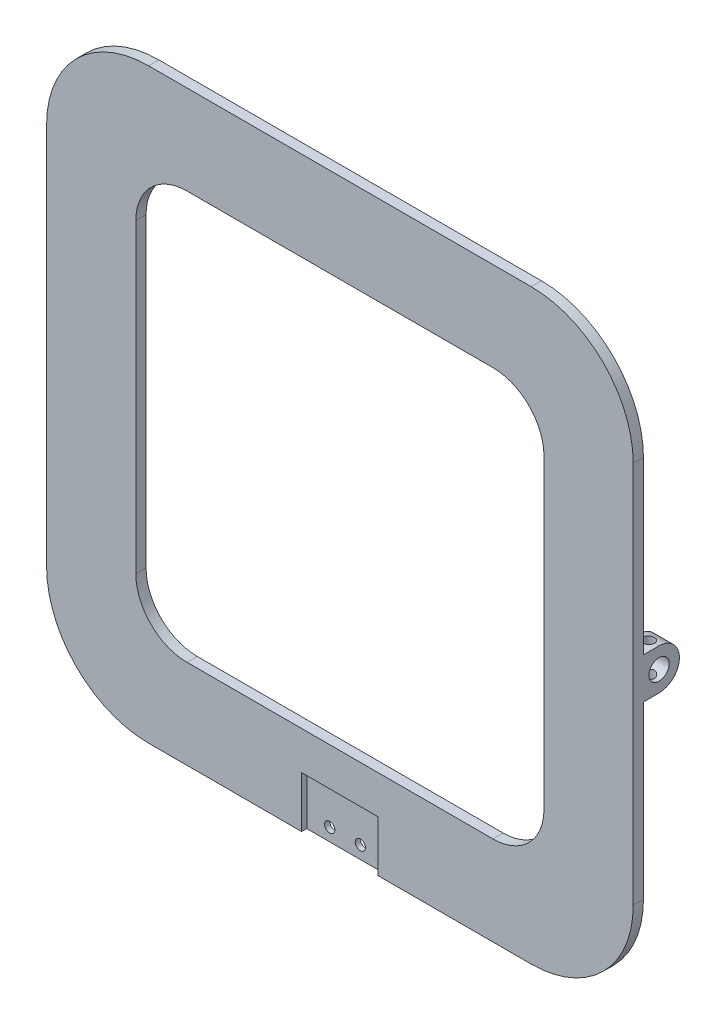
SolidWorks part; units mm, degrees
ref_plane "Płaszczyzna przednia" through (0, 0, 0) normal (0, 0, 1) x (1, 0, 0)
ref_plane "Płaszczyzna górna" through (0, 0, 0) normal (0, 1, 0) x (1, 0, 0)
ref_plane "Płaszczyzna prawa" through (0, 0, 0) normal (1, 0, 0) x (0, 0, -1)
sketch "Szkic1" plane through (0, 0, 0) normal (0, 0, 1) x (1, 0, 0)
  line L0 (0, -57.5) -> (115, -57.5) construction
  line L1 (0, 0) -> (115, 0)
  line L2 (0, 0) -> (0, -115)
  line L3 (0, -115) -> (115, -115)
  line L4 (115, 0) -> (115, -115)
  dimension "D1" = 115
  dimension "D2" = 115
extrude "Dodanie-wyciągnięcie1" add sketch "Szkic1" along normal blind 2
sketch "Szkic3" plane through (115, 0, 0) normal (1, 0, 0) x (0, 0, -1)
  line L0 (0, -115) -> (0, 0) construction
  line L1 (0, -53.5) -> (3.0506, -53.5)
  line L2 (0, -53.5) -> (0, -61.5)
  line L3 (0, -61.5) -> (3.0506, -61.5)
  line L6 (-2, -115) -> (0, -115) construction
  arc A0 (3.0506, -61.5) -> (3.0506, -53.5) centre (3.0506, -57.5) ccw
  dimension "D1" = 8
  dimension "D2" = 53.5
extrude "Dodanie-wyciągnięcie2" add sketch "Szkic3" against normal blind 4
ref_plane "Płaszczyzna1" through (57.5, 0, 0) normal (1, 0, 0) x (0, 0, -1)
mirror "Lustro1" about plane through (57.5, 0, 0) normal (1, 0, 0) of "Dodanie-wyciągnięcie2"
sketch "Szkic5" plane through (115, 0, 0) normal (1, 0, 0) x (0, 0, -1)
  circle A0 centre (3.0506, -57.5) radius 2
  arc A1 (3.0506, -61.5) -> (3.0506, -53.5) centre (3.0506, -57.5) ccw construction
  dimension "D1" = 4
extrude "Wytnij-wyciągnięcie1" cut sketch "Szkic5" against normal through all
sketch "Szkic6" plane through (0, 0, 2) normal (0, 0, 1) x (1, 0, 0)
  line L0 (0, 0) -> (0, -115) construction
  line L2 (0, -115) -> (115, -115) construction
  circle A0 centre (54.5, -112.5) radius 1
  circle A1 centre (60.5, -112.5) radius 1
  dimension "D1" = 2
  dimension "D2" = 2
  dimension "D5" = 2.5
  dimension "D6" = 2.5
  dimension "D3" = 6
  dimension "D4" = 54.5
extrude "Wytnij-wyciągnięcie2" cut sketch "Szkic6" against normal blind 10
fillet "Zaokrąglenie1" radius 20 4 edges at (0, -115, 1) (115, -115, 1) (0, 0, 1) (115, 0, 1)
sketch "Szkic7" plane through (0, 0, 2) normal (0, 0, 1) x (1, 0, 0)
  line L0 (20, -115) -> (95, -115) construction
  line L1 (50, -115) -> (65, -115)
  line L2 (50, -115) -> (50, -105)
  line L3 (50, -105) -> (65, -105)
  line L4 (65, -115) -> (65, -105)
  line L5 (0, -20) -> (0, -95) construction
  dimension "D1" = 10
  dimension "D2" = 15
  dimension "D3" = 50
extrude "Wytnij-wyciągnięcie3" cut sketch "Szkic7" against normal blind 1
sketch "Szkic8" plane through (0, 0, 0) normal (0, 0, -1) x (-1, 0, 0)
  line L0 (0, -20) -> (0, -53.5) construction
  line L1 (-87.5, -97.5) -> (-27.5, -97.5)
  line L2 (-97.5, -87.5) -> (-97.5, -27.5)
  line L3 (-87.5, -17.5) -> (-27.5, -17.5)
  line L4 (-17.5, -87.5) -> (-17.5, -27.5)
  line L5 (-97.5, -97.5) -> (-17.5, -17.5) construction
  line L6 (-97.5, -17.5) -> (-17.5, -97.5) construction
  line L7 (-95, 0) -> (-20, 0) construction
  arc A0 (-87.5, -97.5) -> (-97.5, -87.5) centre (-87.5, -87.5) cw
  arc A1 (-27.5, -97.5) -> (-17.5, -87.5) centre (-27.5, -87.5) ccw
  arc A2 (-27.5, -17.5) -> (-17.5, -27.5) centre (-27.5, -27.5) cw
  arc A3 (-97.5, -27.5) -> (-87.5, -17.5) centre (-87.5, -27.5) cw
  point P0 (-57.5, -57.5)
  dimension "D5" = 10
  dimension "D1" = 80
  dimension "D2" = 80
  dimension "D3" = 17.5
  dimension "D4" = 17.5
extrude "Wytnij-wyciągnięcie4" cut sketch "Szkic8" against normal blind 10
sketch "Szkic9" plane through (0, -53.5, 0) normal (0, 1, 0) x (1, 0, 0)
  line L0 (4, 3.0506) -> (0, 3.0506) construction
  circle A0 centre (2, 3.0506) radius 1.1
extrude "Wytnij-wyciągnięcie5" cut sketch "Szkic9" against normal through all
sketch "Szkic10" plane through (0, -53.5, 0) normal (0, 1, 0) x (1, 0, 0)
  line L0 (111, 3.0506) -> (115, 3.0506) construction
  circle A0 centre (113, 3.0506) radius 1.1
extrude "Wytnij-wyciągnięcie6" cut sketch "Szkic10" against normal blind 10
